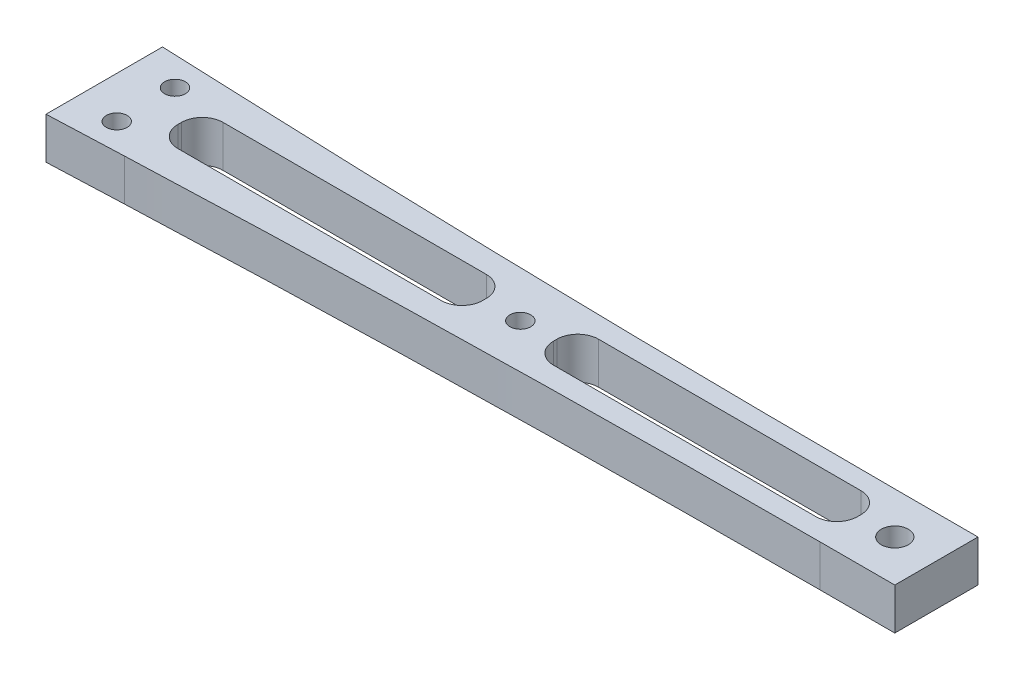
SolidWorks part; units mm, degrees
material "6061-T6 (SS)"
ref_plane "Płaszczyzna przednia" through (0, 0, 0) normal (0, 0, 1) x (1, 0, 0)
ref_plane "Płaszczyzna górna" through (0, 0, 0) normal (0, 1, 0) x (1, 0, 0)
ref_plane "Płaszczyzna prawa" through (0, 0, 0) normal (1, 0, 0) x (0, 0, -1)
sketch "Szkic1" plane through (0, 0, 0) normal (0, 1, 0) x (1, 0, 0)
  line L0 (100, 0) -> (100, 10)
  line L4 (200, 0) -> (200, 20)
  line L5 (0, 10) -> (10, 10)
  line L6 (200, 10) -> (190, 10)
  line L8 (22.9848, 15.5746) -> (86.2594, 15.5746)
  line L9 (17.9848, 10.5746) -> (17.9848, 9.6967)
  line L10 (22.9848, 4.6967) -> (86.2594, 4.6967)
  line L11 (91.2594, 10.5746) -> (91.2594, 9.6967)
  line L12 (113.2251, 15.5746) -> (176.2862, 15.5746)
  line L13 (108.2251, 10.5746) -> (108.2251, 9.7528)
  line L14 (113.2251, 4.7528) -> (176.2862, 4.7528)
  line L15 (181.2862, 10.5746) -> (181.2862, 9.7528)
  line L16 (10, 3) -> (10, 17)
  line L17 (0, -4) -> (100, 0)
  line L18 (200, 0) -> (100, 0)
  line L19 (200, 20) -> (100, 20)
  line L20 (100, 20) -> (0, 24)
  line L21 (0, 24) -> (0, -4)
  circle A0 centre (100, 10) radius 1.971
  circle A2 centre (190, 10) radius 3.25
  arc A3 (176.2862, 4.7528) -> (181.2862, 9.7528) centre (176.2862, 9.7528) ccw
  arc A4 (181.2862, 10.5746) -> (176.2862, 15.5746) centre (176.2862, 10.5746) ccw
  arc A5 (113.2251, 4.7528) -> (108.2251, 9.7528) centre (113.2251, 9.7528) cw
  arc A6 (113.2251, 15.5746) -> (108.2251, 10.5746) centre (113.2251, 10.5746) ccw
  arc A7 (17.9848, 9.6967) -> (22.9848, 4.6967) centre (22.9848, 9.6967) ccw
  arc A8 (86.2594, 4.6967) -> (91.2594, 9.6967) centre (86.2594, 9.6967) ccw
  arc A9 (91.2594, 10.5746) -> (86.2594, 15.5746) centre (86.2594, 10.5746) ccw
  arc A10 (22.9848, 15.5746) -> (17.9848, 10.5746) centre (22.9848, 10.5746) ccw
  circle A11 centre (10, 17) radius 2.5
  circle A12 centre (10, 3) radius 2.5
  point P39 (0, 10)
  point P42 (10, 10)
  dimension "D1" = 5
extrude "Dodanie-wyciągnięcie1" add sketch "Szkic1" along normal blind 10 contours A0 L4 region at (49.9193, 0, -0.0179)
fillet "Zaokrąglenie1" radius 4100 2 edges at (100, 5, -20) (100, 5, 0)
hole_wizard "Otwór gwintowany M62" positions "Szkic 3D2" profile "Szkic3" tap size "M6" standard "ISO"
sketch3d "Szkic 3D2"
  line L0 (100, 10, -10) -> (100, 0, -10) construction
  point P0 (100, 10, -10)
sketch "Szkic3" plane through (100, 10, -10) normal (1, 0, 0) x (0, 0, 1)
  line L0 (0, 0) -> (0, 17)
  line L1 (0, 17) -> (2.5, 15.4978)
  line L2 (2.5, 15.4978) -> (2.5, 0)
  line L5 (2.5, 0) -> (0, 0)
  line L10 (0, 17) -> (-2.5, 15.4978) construction
  line L11 (0, -6.35) -> (0, 107.95) construction
  dimension "Średnica wiertła gwintu" = 5
  dimension "Głębokość otworu gwintowanego" = 17
  dimension "Kąt wiertła" = 118
cosmetic thread "Gwint otworu1" parameters "D1"=12, "D2"=6
